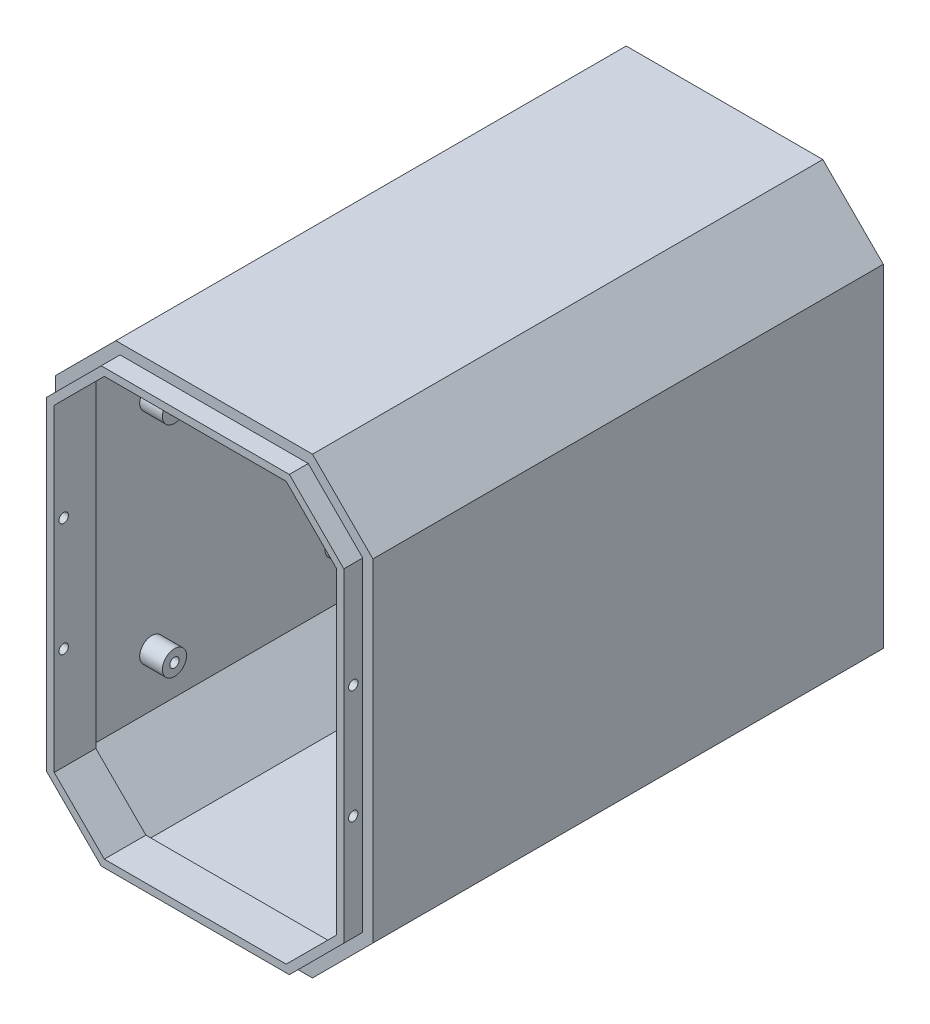
SolidWorks part; units mm, degrees
ref_plane "Front Plane" through (0, 0, 0) normal (0, 0, 1) x (1, 0, 0)
ref_plane "Top Plane" through (0, 0, 0) normal (0, 1, 0) x (1, 0, 0)
ref_plane "Right Plane" through (0, 0, 0) normal (1, 0, 0) x (0, 0, -1)
ref_plane "PZ_p33_000" through (0, 0, 33) normal (0, 0, 1) x (1, 0, 0)
sketch "S_prism1" plane through (0, 0, 33) normal (0, 0, 1) x (1, 0, 0)
  line L0 (42, -44) -> (42, 44)
  line L1 (42, 44) -> (26, 60)
  line L2 (26, 60) -> (-26, 60)
  line L3 (-26, 60) -> (-42, 44)
  line L4 (-42, 44) -> (-42, -44)
  line L5 (-42, -44) -> (-26, -60)
  line L6 (-26, -60) -> (26, -60)
  line L7 (26, -60) -> (42, -44)
extrude "Boss_1" add sketch "S_prism1" along normal blind 135
ref_plane "PZ_p71_125" through (0, 0, 71.125) normal (0, 0, 1) x (1, 0, 0)
sketch "S_pcut2" plane through (0, 0, 71.125) normal (0, 0, 1) x (1, 0, 0)
  line L0 (39.5, -42.9645) -> (39.5, 42.9645)
  line L1 (39.5, 42.9645) -> (24.9645, 57.5)
  line L2 (24.9645, 57.5) -> (-24.9645, 57.5)
  line L3 (-24.9645, 57.5) -> (-39.5, 42.9645)
  line L4 (-39.5, 42.9645) -> (-39.5, -42.9645)
  line L5 (-39.5, -42.9645) -> (-24.9645, -57.5)
  line L6 (-24.9645, -57.5) -> (24.9645, -57.5)
  line L7 (24.9645, -57.5) -> (39.5, -42.9645)
extrude "Cut_2" cut sketch "S_pcut2" along normal blind 96.975
ref_plane "PZ_p32_900" through (0, 0, 32.9) normal (0, 0, 1) x (1, 0, 0)
sketch "S_pcut3" plane through (0, 0, 32.9) normal (0, 0, 1) x (1, 0, 0)
  line L0 (39.5, -42.9645) -> (39.5, 42.9645)
  line L1 (39.5, 42.9645) -> (24.9645, 57.5)
  line L2 (24.9645, 57.5) -> (-24.9645, 57.5)
  line L3 (-24.9645, 57.5) -> (-39.5, 42.9645)
  line L4 (-39.5, 42.9645) -> (-39.5, -42.9645)
  line L5 (-39.5, -42.9645) -> (-24.9645, -57.5)
  line L6 (-24.9645, -57.5) -> (24.9645, -57.5)
  line L7 (24.9645, -57.5) -> (39.5, -42.9645)
extrude "Cut_3" cut sketch "S_pcut3" along normal blind 35.725
ref_plane "PZ_p68_525" through (0, 0, 68.525) normal (0, 0, 1) x (1, 0, 0)
sketch "S_cut4" plane through (0, 0, 68.525) normal (0, 0, 1) x (1, 0, 0)
  line L0 (-34, -14) -> (-26, -14)
  line L1 (-26, -14) -> (-26, 14)
  line L2 (-26, 14) -> (-34, 14)
  line L3 (-34, 14) -> (-34, -14)
  dimension "P1" = 34
  dimension "P2" = 14
  dimension "P3" = 26
  dimension "P4" = 14
  dimension "P5" = 26
  dimension "P6" = 14
  dimension "P7" = 34
  dimension "P8" = 14
extrude "Pocket_4" cut sketch "S_cut4" along normal blind 2.7
ref_plane "PX_m42_100" through (-42.1, 0, 0) normal (1, 0, 0) x (0, 0, -1)
sketch "S_hole5" plane through (-42.1, 0, 0) normal (1, 0, 0) x (0, 0, -1)
  circle A0 centre (-88, 0) radius 6
  dimension "D1_S_hole5" = 12
  dimension "P2" = 88
extrude "Hole_5" cut sketch "S_hole5" along normal blind 2.7
sketch "S_hole6" plane through (0, 0, 68.525) normal (0, 0, 1) x (1, 0, 0)
  circle A0 centre (-20, -25) radius 1.6
  dimension "D1_S_hole6" = 3.2
  dimension "P2" = 20
  dimension "P3" = 25
extrude "Hole_6" cut sketch "S_hole6" along normal blind 2.7
sketch "S_hole7" plane through (0, 0, 68.525) normal (0, 0, 1) x (1, 0, 0)
  circle A0 centre (-20, 25) radius 1.6
  dimension "D1_S_hole7" = 3.2
  dimension "P2" = 20
  dimension "P3" = 25
extrude "Hole_7" cut sketch "S_hole7" along normal blind 2.7
sketch "S_hole8" plane through (0, 0, 68.525) normal (0, 0, 1) x (1, 0, 0)
  circle A0 centre (24, -25) radius 1.6
  dimension "D1_S_hole8" = 3.2
  dimension "P2" = 24
  dimension "P3" = 25
extrude "Hole_8" cut sketch "S_hole8" along normal blind 2.7
sketch "S_hole9" plane through (0, 0, 68.525) normal (0, 0, 1) x (1, 0, 0)
  circle A0 centre (24, 25) radius 1.6
  dimension "D1_S_hole9" = 3.2
  dimension "P2" = 24
  dimension "P3" = 25
extrude "Hole_9" cut sketch "S_hole9" along normal blind 2.7
ref_plane "PZ_p162_000" through (0, 0, 162) normal (0, 0, 1) x (1, 0, 0)
sketch "S_prism10" plane through (0, 0, 162) normal (0, 0, 1) x (1, 0, 0)
  line L0 (40, -43.1716) -> (40, 43.1716)
  line L1 (40, 43.1716) -> (25.1716, 58)
  line L2 (25.1716, 58) -> (-25.1716, 58)
  line L3 (-25.1716, 58) -> (-40, 43.1716)
  line L4 (-40, 43.1716) -> (-40, -43.1716)
  line L5 (-40, -43.1716) -> (-25.1716, -58)
  line L6 (-25.1716, -58) -> (25.1716, -58)
  line L7 (25.1716, -58) -> (40, -43.1716)
extrude "Boss_10" add sketch "S_prism10" along normal blind 6
ref_plane "PZ_p167_900" through (0, 0, 167.9) normal (0, 0, 1) x (1, 0, 0)
sketch "S_prism11" plane through (0, 0, 167.9) normal (0, 0, 1) x (1, 0, 0)
  line L0 (39.3, -42.8816) -> (39.3, 42.8816)
  line L1 (39.3, 42.8816) -> (24.8816, 57.3)
  line L2 (24.8816, 57.3) -> (-24.8816, 57.3)
  line L3 (-24.8816, 57.3) -> (-39.3, 42.8816)
  line L4 (-39.3, 42.8816) -> (-39.3, -42.8816)
  line L5 (-39.3, -42.8816) -> (-24.8816, -57.3)
  line L6 (-24.8816, -57.3) -> (24.8816, -57.3)
  line L7 (24.8816, -57.3) -> (39.3, -42.8816)
extrude "Boss_11" add sketch "S_prism11" along normal blind 5.1
ref_plane "PX_m40_000" through (-40, 0, 0) normal (1, 0, 0) x (0, 0, -1)
sketch "S_cyl12" plane through (-40, 0, 0) normal (1, 0, 0) x (0, 0, -1)
  circle A0 centre (-96, -29) radius 3.2
  dimension "D1_S_cyl12" = 6.4
  dimension "P2" = 96
  dimension "P3" = 29
extrude "Boss_12" add sketch "S_cyl12" along normal blind 6.5
sketch "S_cyl13" plane through (-40, 0, 0) normal (1, 0, 0) x (0, 0, -1)
  circle A0 centre (-145, -29) radius 3.2
  dimension "D1_S_cyl13" = 6.4
  dimension "P2" = 145
  dimension "P3" = 29
extrude "Boss_13" add sketch "S_cyl13" along normal blind 6.5
sketch "S_cyl14" plane through (-40, 0, 0) normal (1, 0, 0) x (0, 0, -1)
  circle A0 centre (-96, 29) radius 3.2
  dimension "D1_S_cyl14" = 6.4
  dimension "P2" = 96
  dimension "P3" = 29
extrude "Boss_14" add sketch "S_cyl14" along normal blind 6.5
sketch "S_cyl15" plane through (-40, 0, 0) normal (1, 0, 0) x (0, 0, -1)
  circle A0 centre (-145, 29) radius 3.2
  dimension "D1_S_cyl15" = 6.4
  dimension "P2" = 145
  dimension "P3" = 29
extrude "Boss_15" add sketch "S_cyl15" along normal blind 6.5
ref_plane "PZ_p161_900" through (0, 0, 161.9) normal (0, 0, 1) x (1, 0, 0)
sketch "S_pcut16" plane through (0, 0, 161.9) normal (0, 0, 1) x (1, 0, 0)
  line L0 (37.3, -42.0532) -> (37.3, 42.0532)
  line L1 (37.3, 42.0532) -> (24.0532, 55.3)
  line L2 (24.0532, 55.3) -> (-24.0532, 55.3)
  line L3 (-24.0532, 55.3) -> (-37.3, 42.0532)
  line L4 (-37.3, 42.0532) -> (-37.3, -42.0532)
  line L5 (-37.3, -42.0532) -> (-24.0532, -55.3)
  line L6 (-24.0532, -55.3) -> (24.0532, -55.3)
  line L7 (24.0532, -55.3) -> (37.3, -42.0532)
extrude "Cut_16" cut sketch "S_pcut16" along normal blind 11.2
ref_plane "PX_p37_100" through (37.1, 0, 0) normal (1, 0, 0) x (0, 0, -1)
sketch "S_hole17" plane through (37.1, 0, 0) normal (1, 0, 0) x (0, 0, -1)
  circle A0 centre (-170.5, -15) radius 1.25
  dimension "D1_S_hole17" = 2.5
  dimension "P2" = 170.5
  dimension "P3" = 15
extrude "Hole_17" cut sketch "S_hole17" along normal blind 2.7
sketch "S_hole18" plane through (37.1, 0, 0) normal (1, 0, 0) x (0, 0, -1)
  circle A0 centre (-170.5, 15) radius 1.25
  dimension "D1_S_hole18" = 2.5
  dimension "P2" = 170.5
  dimension "P3" = 15
extrude "Hole_18" cut sketch "S_hole18" along normal blind 2.7
ref_plane "PX_m39_800" through (-39.8, 0, 0) normal (1, 0, 0) x (0, 0, -1)
sketch "S_hole19" plane through (-39.8, 0, 0) normal (1, 0, 0) x (0, 0, -1)
  circle A0 centre (-170.5, -15) radius 1.25
  dimension "D1_S_hole19" = 2.5
  dimension "P2" = 170.5
  dimension "P3" = 15
extrude "Hole_19" cut sketch "S_hole19" along normal blind 2.7
sketch "S_hole20" plane through (-39.8, 0, 0) normal (1, 0, 0) x (0, 0, -1)
  circle A0 centre (-170.5, 15) radius 1.25
  dimension "D1_S_hole20" = 2.5
  dimension "P2" = 170.5
  dimension "P3" = 15
extrude "Hole_20" cut sketch "S_hole20" along normal blind 2.7
ref_plane "PX_m39_500" through (-39.5, 0, 0) normal (1, 0, 0) x (0, 0, -1)
sketch "S_hole21" plane through (-39.5, 0, 0) normal (1, 0, 0) x (0, 0, -1)
  circle A0 centre (-96, -29) radius 1.25
  dimension "D1_S_hole21" = 2.5
  dimension "P2" = 96
  dimension "P3" = 29
extrude "Hole_21" cut sketch "S_hole21" along normal blind 6.1
sketch "S_hole22" plane through (-39.5, 0, 0) normal (1, 0, 0) x (0, 0, -1)
  circle A0 centre (-145, -29) radius 1.25
  dimension "D1_S_hole22" = 2.5
  dimension "P2" = 145
  dimension "P3" = 29
extrude "Hole_22" cut sketch "S_hole22" along normal blind 6.1
sketch "S_hole23" plane through (-39.5, 0, 0) normal (1, 0, 0) x (0, 0, -1)
  circle A0 centre (-96, 29) radius 1.25
  dimension "D1_S_hole23" = 2.5
  dimension "P2" = 96
  dimension "P3" = 29
extrude "Hole_23" cut sketch "S_hole23" along normal blind 6.1
sketch "S_hole24" plane through (-39.5, 0, 0) normal (1, 0, 0) x (0, 0, -1)
  circle A0 centre (-145, 29) radius 1.25
  dimension "D1_S_hole24" = 2.5
  dimension "P2" = 145
  dimension "P3" = 29
extrude "Hole_24" cut sketch "S_hole24" along normal blind 6.1
equation "\"plate_t\" = 3"
equation "\"clearance\" = 0.4"
